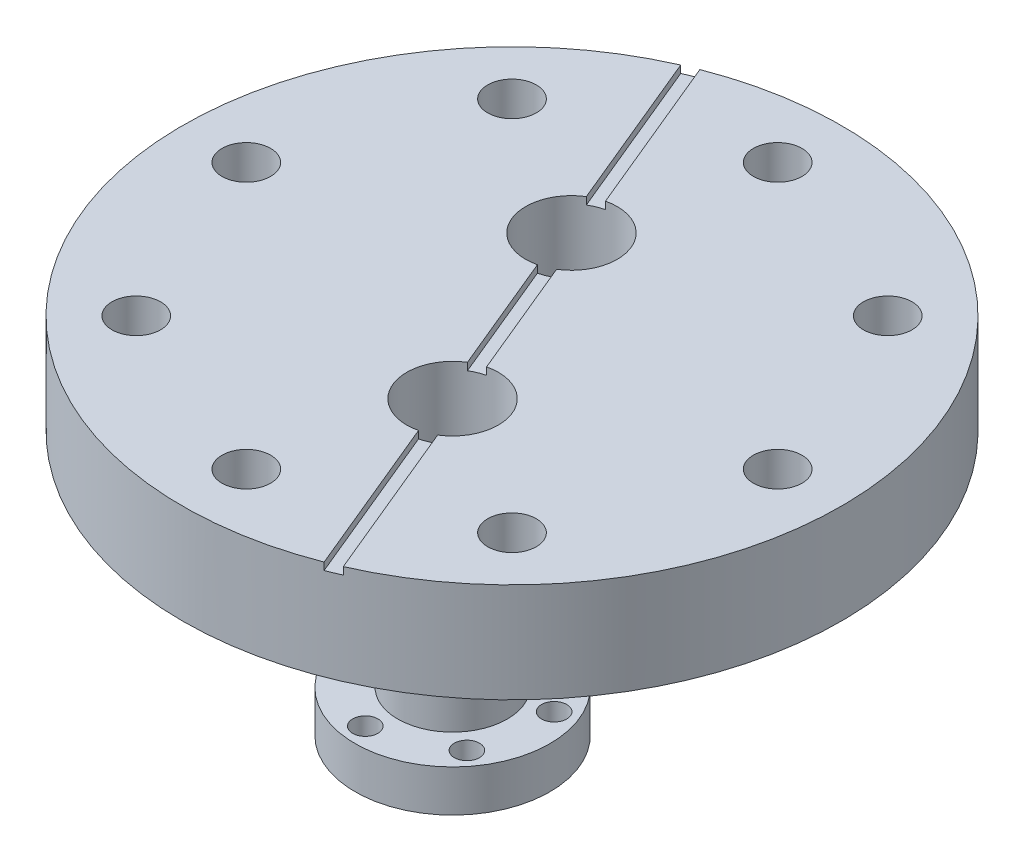
SolidWorks part; units mm, degrees
ref_plane "Front Plane" through (0, 0, 0) normal (0, 0, 1) x (1, 0, 0)
ref_plane "Top Plane" through (0, 0, 0) normal (0, 1, 0) x (1, 0, 0)
ref_plane "Right Plane" through (0, 0, 0) normal (1, 0, 0) x (0, 0, -1)
sketch "Sketch1" plane through (0, 0, 0) normal (0, 1, 0) x (1, 0, 0)
  circle A0 centre (0, 0) radius 57.15
  dimension "D1" = 114.3
extrude "Extrude1" add sketch "Sketch1" along normal blind 17.272
sketch "Sketch3" plane through (0, 0, 0) normal (0, -1, 0) x (1, 0, 0)
  circle A0 centre (0, 46.0756) radius 4.2164
  dimension "D1" = 8.4328
  dimension "D2" = 46.0756
extrude "Extrude2" cut sketch "Sketch3" against normal through all
pattern_circular "CirPattern1" count 8 over 360 about axis through (0, 17.272, 0) along (0, -1, 0) of "Extrude2"
sketch "Sketch5" plane through (0, 0, 0) normal (0, -1, 0) x (1, 0, 0)
  line L0 (0, 0) -> (27.6852, 66.838) construction
  line L1 (0, 0) -> (0, 46.0756) construction
  circle A0 centre (7.2901, 17.5999) radius 7.9375
  circle A1 centre (7.2901, 17.5999) radius 9.4996
  dimension "D2" = 15.875
  dimension "D3" = 18.9992
  dimension "D1" = 22.5
  dimension "D4" = 19.05
extrude "Extrude3" add sketch "Sketch5" along normal blind 33.3375
sketch "Sketch6" plane through (0, -33.3375, 0) normal (0, -1, 0) x (1, 0, 0)
  circle A0 centre (7.2901, 17.5999) radius 7.9375
  circle A1 centre (7.2901, 17.5999) radius 16.891
  dimension "D1" = 33.782
extrude "Extrude4" add sketch "Sketch6" against normal blind 7.239
sketch "Sketch7" plane through (0, -33.3375, 0) normal (0, -1, 0) x (1, 0, 0)
  line L0 (7.2901, 17.5999) -> (0, 0) construction
  line L1 (7.2901, 17.5999) -> (-12.2066, 2.6395) construction
  circle A0 centre (-3.4102, 9.3893) radius 2.1844
  dimension "D3" = 4.3688
  dimension "D1" = 30
  dimension "D2" = 13.4874
extrude "Extrude5" cut sketch "Sketch7" against normal up to next
pattern_circular "CirPattern2" count 6 over 360 about axis through (7.2901, -33.3375, 17.5999) along (0, 1, 0) of "Extrude5"
sketch "Sketch8" plane through (0, -33.3375, 0) normal (0, -1, 0) x (1, 0, 0)
  circle A0 centre (7.2901, 17.5999) radius 7.9375
extrude "Extrude6" cut sketch "Sketch8" against normal through all
sketch "Sketch9" plane through (0, 0, 0) normal (0, -1, 0) x (1, 0, 0)
  line L0 (0, 0) -> (-25.2111, -60.865) construction
  line L1 (0, 0) -> (0, -27.3134) construction
  circle A0 centre (-7.2901, -17.5999) radius 16.891
  circle A1 centre (-7.2901, -17.5999) radius 7.9375
  dimension "D2" = 33.782
  dimension "D3" = 15.875
  dimension "D1" = 22.5
  dimension "D4" = 19.05
extrude "Extrude7" add sketch "Sketch9" along normal blind 7.239
sketch "Sketch11" plane through (0, -7.239, 0) normal (0, -1, 0) x (1, 0, 0)
  circle A0 centre (-7.2901, -17.5999) radius 7.9375
extrude "Extrude8" cut sketch "Sketch11" against normal through all
sketch "Sketch12" plane through (0, -7.239, 0) normal (0, -1, 0) x (1, 0, 0)
  line L0 (-7.2901, -17.5999) -> (0, 0) construction
  line L1 (-7.2901, -17.5999) -> (14.1049, -1.1829) construction
  circle A0 centre (3.4102, -9.3893) radius 2.1844
  dimension "D2" = 4.3688
  dimension "D1" = 30
  dimension "D3" = 13.4874
extrude "Extrude9" cut sketch "Sketch12" against normal blind 7.239
pattern_circular "CirPattern3" count 6 over 360 about axis through (-7.2901, -7.239, -17.5999) along (0, 1, 0) of "Extrude9"
sketch "Sketch13" plane through (0, 17.272, 0) normal (0, 1, 0) x (1, 0, 0)
  line L0 (-7.2901, 17.5999) -> (7.2901, -17.5999) construction
  line L1 (-24.156, 61.6363) -> (-26.5026, 60.6643)
  line L2 (-26.5026, 60.6643) -> (25.6606, -65.2689)
  line L3 (25.6606, -65.2689) -> (28.0073, -64.2969)
  line L4 (-24.156, 61.6363) -> (28.0073, -64.2969)
  point P10 (26.8339, -64.7829)
  point P11 (-25.3293, 61.1503)
  dimension "D1" = 2.54
extrude "Extrude10" cut sketch "Sketch13" against normal blind 1.27
